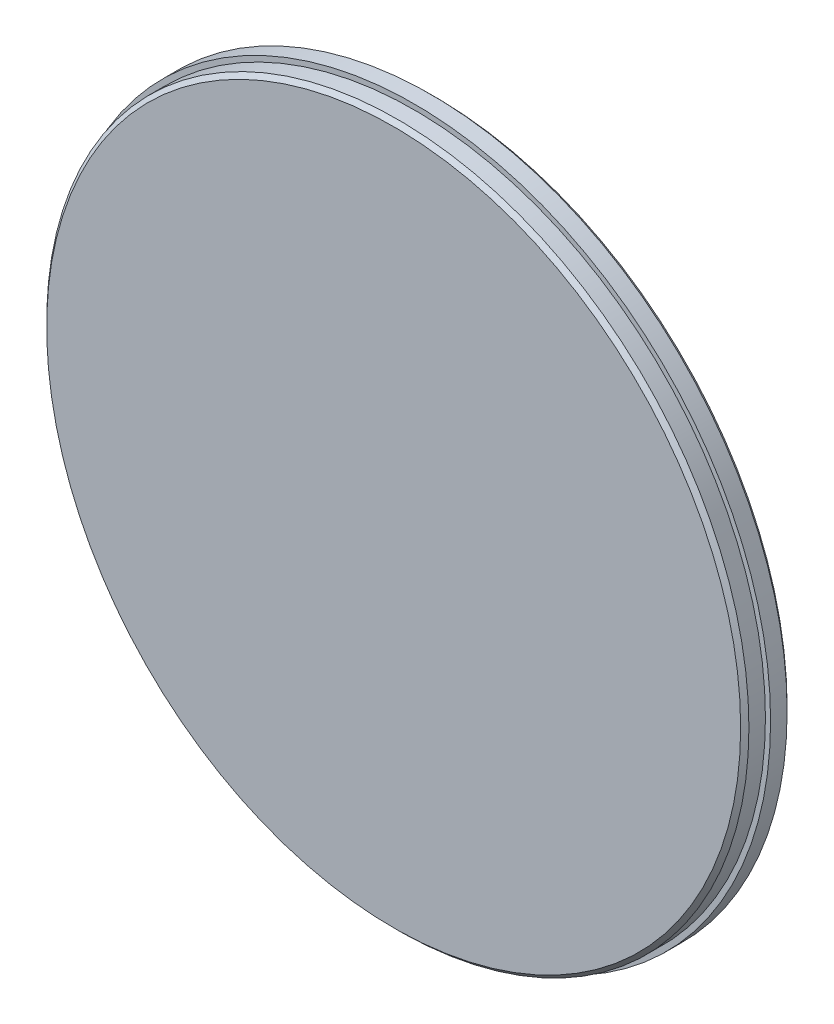
SolidWorks part; units mm, degrees
ref_plane "Front Plane" through (0, 0, 0) normal (0, 0, 1) x (1, 0, 0)
ref_plane "Top Plane" through (0, 0, 0) normal (0, 1, 0) x (1, 0, 0)
ref_plane "Right Plane" through (0, 0, 0) normal (1, 0, 0) x (0, 0, -1)
sketch "Sketch1" plane through (0, 0, 0) normal (0, 0, 1) x (1, 0, 0)
  circle A0 centre (0, 0) radius 17.25
  circle A1 centre (0, 0) radius 17
  dimension "D1" = 34.5
  dimension "D2" = 34
extrude "Boss-Extrude1" add sketch "Sketch1" along normal blind 1
extrude "Boss-Extrude2" add sketch "Sketch1<2>" along normal blind 2 contours A1 region at (0, 0, 0)
sketch "Sketch1<2>" plane through (0, 0, 0) normal (0, 0, 1) x (1, 0, 0) same geometry as "Sketch1"
chamfer "Chamfer1" distance 0.2 angle 45 2 edges at (17.25, 0, 0) (17, 0, 2)
